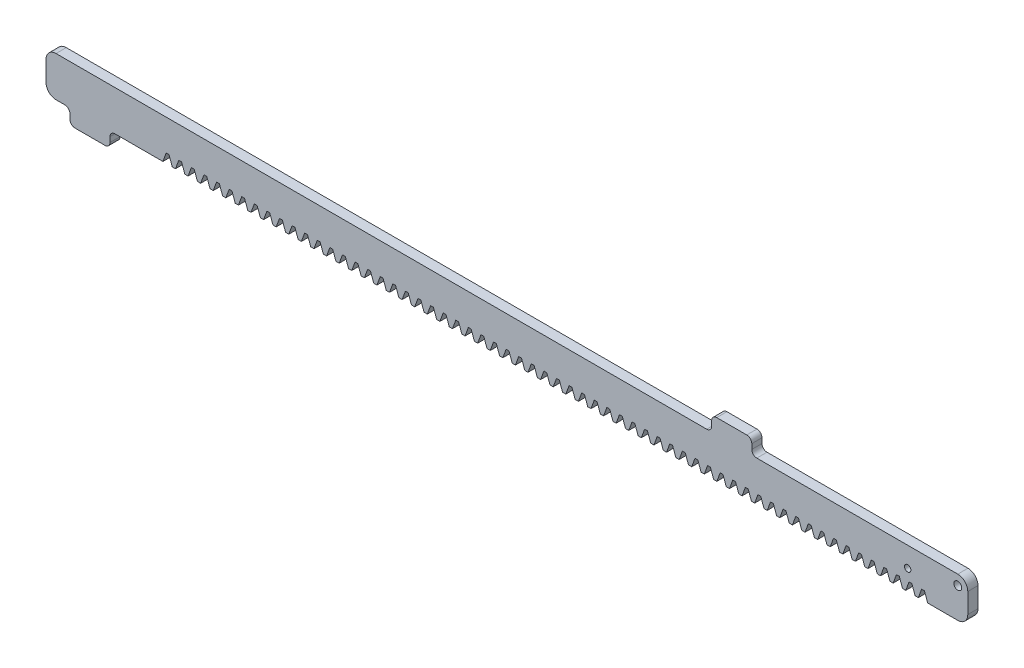
SolidWorks part; units mm, degrees
material "PC High Viscosity"
ref_plane "Front Plane" through (0, 0, 0) normal (0, 0, 1) x (1, 0, 0)
ref_plane "Top Plane" through (0, 0, 0) normal (0, 1, 0) x (1, 0, 0)
ref_plane "Right Plane" through (0, 0, 0) normal (1, 0, 0) x (0, 0, -1)
sketch "Sketch1" plane through (0, 0, 0) normal (0, 0, 1) x (1, 0, 0)
  line L1 (0, 0) -> (15.1307, 0)
  line L2 (0, 0) -> (0, 25.4)
  line L3 (0, 25.4) -> (40.5308, 25.4)
  line L4 (584.2, 0) -> (584.2, 25.4)
  line L7 (533.4, 25.4) -> (584.2, 25.4)
  line L8 (40.5308, 25.4) -> (421.9033, 25.4)
  line L9 (40.5307, 0) -> (584.2, 0)
  line L11 (584.2, 22.7162) -> (577.85, 26.3823) construction
  line L12 (577.85, 26.3823) -> (571.5, 22.7162) construction
  line L13 (571.5, 22.7162) -> (571.5, 15.3838) construction
  line L14 (571.5, 15.3838) -> (577.85, 11.7177) construction
  line L15 (577.85, 11.7177) -> (584.2, 15.3838) construction
  line L16 (584.2, 15.3838) -> (584.2, 22.7162) construction
  line L19 (590.55, 0) -> (590.55, 10.0162) construction
  line L20 (590.55, 10.0162) -> (76.2, 10.0162) construction
  line L21 (76.2, 10.0162) -> (76.2, 0) construction
  line L22 (447.3033, 25.4) -> (533.4, 25.4)
  line L26 (15.1307, 0) -> (15.1307, -9.525)
  line L27 (15.1307, -9.525) -> (40.5307, -9.525)
  line L28 (40.5307, -9.525) -> (40.5307, 0)
  line L29 (421.9033, 25.4) -> (421.9033, 34.925)
  line L30 (421.9033, 34.925) -> (447.3033, 34.925)
  line L31 (447.3033, 34.925) -> (447.3033, 25.4)
  circle A0 centre (577.85, 19.05) radius 2.4892
  circle A1 centre (577.85, 19.05) radius 6.35 construction
  dimension "D5" = 4.9784
  dimension "D6" = 40.5307
  dimension "D7" = 12.7
  dimension "D1" = 584.2
  dimension "D2" = 25.4
  dimension "D3" = 421.9033
  dimension "D4" = 9.525
  dimension "D8" = 25.4
  dimension "D9" = 25.4
extrude "Boss-Extrude1" add sketch "Sketch1" along normal blind 6.477 contours L3 | L1 L4 L3 L2 A0 | L1 region at (289.8115, 12.6919, 0)
fillet "Fillet2" radius 6.35 4 edges at (0, 0, 3.2385) (0, 25.4, 3.2385) (584.2, 25.4, 3.2385) (584.2, 0, 3.2385)
sketch "Sketch2" plane through (0, 0, 6.477) normal (0, 0, 1) x (1, 0, 0)
  line L0 (558.8, 0) -> (43.7057, 0)
  line L1 (43.7057, 0) -> (43.7057, 5.715)
  line L2 (43.7057, 5.715) -> (558.8, 5.715)
  line L3 (558.8, 5.715) -> (558.8, 0)
  line L5 (557.8755, 2.54) -> (549.711, 2.54) construction
  line L6 (558.8, 0) -> (556.7199, 5.715)
  line L7 (40.5307, 0) -> (552.8688, 0) construction
  line L8 (552.8688, 0) -> (558.8, 0)
  line L10 (556.7199, 5.715) -> (554.9488, 5.715)
  line L11 (558.8, 0) -> (552.8688, 0)
  line L12 (552.8688, 0) -> (554.9488, 5.715)
  line L13 (554.9488, 5.715) -> (556.7199, 5.715)
  line L14 (558.8, 0) -> (552.8688, 0)
  line L15 (554.9488, 5.715) -> (556.7199, 5.715)
  line L16 (558.8, 0) -> (552.8688, 0)
  line L17 (552.8688, 0) -> (558.8, 0)
  line L19 (556.7199, 5.715) -> (554.9488, 5.715) construction
  line L20 (552.8688, 0) -> (558.8, 0) construction
  line L21 (0, 0) -> (15.1307, 0) construction
  line L22 (584.2, 0) -> (584.2, 25.4) construction
  line L23 (40.5307, 0) -> (584.2, 0) construction
  point P8 (553.7932, 2.54)
  point P16 (557.8755, 2.54)
  dimension "D1" = 70
  dimension "D2" = 2.54
  dimension "D3" = 3.175
  dimension "D4" = 70
  dimension "D5" = 1.7711
  dimension "D6" = 25.4
extrude "Cut-Extrude1" cut sketch "Sketch2" against normal through all contours L12 L0 L8 L6 L2 region at (555.8344, 2.343, 6.477)
pattern_linear "LPattern1" count 61 spacing 7.9796 along (-1, 0, 0) of "Cut-Extrude1"
sketch "Sketch3" plane through (0, 0, 6.477) normal (0, 0, 1) x (1, 0, 0)
  line L2 (533.4, 25.4) -> (584.2, 25.4) construction
  line L3 (584.2, 0) -> (584.2, 25.4) construction
  circle A0 centre (546.1, 12.7) radius 2.0193
  dimension "D2" = 4.0386
  dimension "D1" = 12.7
  dimension "D3" = 38.1
extrude "Cut-Extrude2" cut sketch "Sketch3" against normal through all
fillet "Fillet3" radius 3.175 8 edges at (421.9033, 25.4, 3.2385) (421.9033, 34.925, 3.2385) (447.3033, 34.925, 3.2385) (447.3033, 25.4, 3.2385) (40.5307, -9.525, 3.2385) (40.5307, 0, 3.2385) (15.1307, -9.525, 3.2385) (15.1307, 0, 3.2385)
